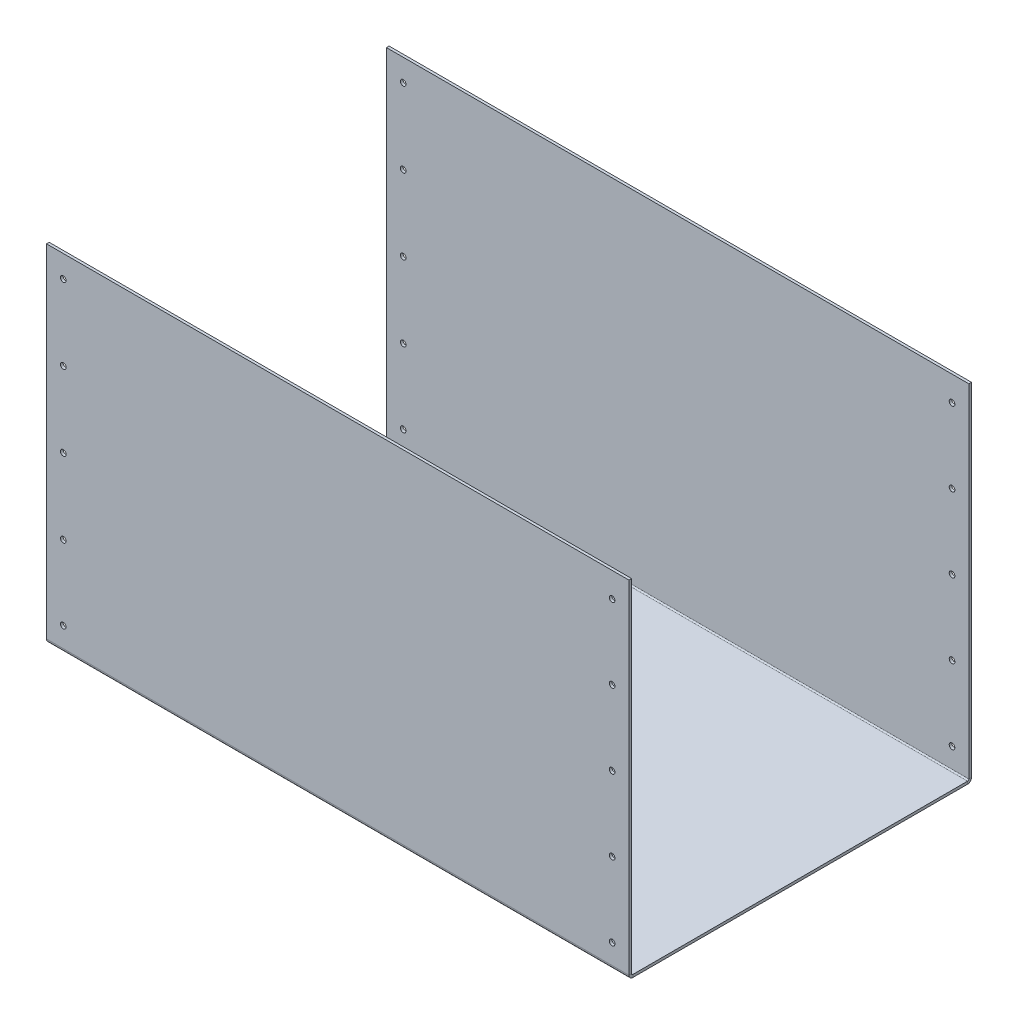
SolidWorks part; units mm, degrees
note: The reader was unsure of these and kept them because the rebuilt part matched: flange length of "Ребро-кромка1".
ref_plane "Спереди" through (0, 0, 0) normal (0, 0, 1) x (1, 0, 0)
ref_plane "Сверху" through (0, 0, 0) normal (0, 1, 0) x (1, 0, 0)
ref_plane "Справа" through (0, 0, 0) normal (1, 0, 0) x (0, 0, -1)
sketch "Эскиз1" plane through (0, 0, 0) normal (0, 1, 0) x (1, 0, 0)
  line L1 (-162.679, 129.9004) -> (166.321, 129.9004)
  line L2 (-162.679, 129.9004) -> (-162.679, -63.5996)
  line L3 (-162.679, -63.5996) -> (166.321, -63.5996)
  line L4 (166.321, 129.9004) -> (166.321, -63.5996)
  dimension "D1" = 329
  dimension "D2" = 193.5
base flange "Базовая кромка1" sketch "Эскиз1" thickness 1.5 reverse thickness direction no parameters "D1"=0.7366
edge flange "Ребро-кромка1" sketch "Эскиз18" flange profiles "Эскиз18", "Эскиз19" flange angle 90 flange length 194 flange position material inside bend radius 0.7366 thickness 1.5 relief rectangular parameters "D6"=10, "D8"=1
sketch "Эскиз18" plane through (0, 0, -129.9004) normal (0, 0, -1) x (-1, 0, 0)
  line L2 (-166.321, 0) -> (-166.321, 194)
  line L3 (-166.321, 194) -> (162.679, 194)
  line L4 (162.679, 194) -> (162.679, 0)
  line L5 (-166.321, 0) -> (162.679, 0) construction
  line L6 (-166.321, 0) -> (162.679, 0)
sketch "Эскиз19" plane through (0, 0, 63.5996) normal (0, 0, 1) x (1, 0, 0)
  line L0 (-162.679, 0) -> (166.321, 0) construction
  line L1 (-162.679, 0) -> (166.321, 0)
  line L2 (-162.679, 0) -> (-162.679, 194)
  line L3 (-162.679, 194) -> (166.321, 194)
  line L4 (166.321, 194) -> (166.321, 0)
bend "EdgeBend1" bend radius 0.7366 bend angle 90 parameters "D5"=1
bend "EdgeBend2" bend radius 0.7366 bend angle 90 parameters "D5"=2
sketch "Эскиз21" plane through (0, 0, -129.9004) normal (0, 0, -1) x (-1, 0, 0)
  line L0 (162.679, -1.5) -> (-166.321, -1.5) construction
  line L1 (-166.321, 194) -> (-166.321, 0.7366) construction
  line L2 (153.179, 181.5) -> (153.179, 12) construction
  line L3 (162.679, 0.7366) -> (162.679, 194) construction
  circle A0 centre (-156.821, 12) radius 1.6
  circle A1 centre (-156.821, 54) radius 1.6
  circle A2 centre (-156.821, 96) radius 1.6
  circle A3 centre (-156.821, 138) radius 1.6
  circle A4 centre (-156.821, 180) radius 1.6
  circle A5 centre (153.179, 181.5) radius 1.6
  circle A6 centre (153.179, 139) radius 1.6
  circle A7 centre (153.179, 96.5) radius 1.6
  circle A8 centre (153.179, 54) radius 1.6
  circle A9 centre (153.179, 12) radius 1.6
  dimension "D1" = 13.5
  dimension "D2" = 9.5
  dimension "D3" = 3.2
  dimension "D6" = 13.5
  dimension "D7" = 42
  dimension "D8" = 42.5
  dimension "D9" = 42.5
  dimension "D10" = 42.5
  dimension "D5" = 9.5
  dimension "D4" = 5
extrude "Вырез-Вытянуть2" cut sketch "Эскиз21" against normal blind 217 normal cut yes
sketch "Сгиб-Линии1" plane through (0, 0, 0) normal (0, 1, 0) x (1, 0, 0)
sketch "Граничная рамка1" plane through (0, 0, 0) normal (0, 1, 0) x (1, 0, 0)
sheet metal parameters "Листовой металл3" thickness 1.5 parameters "D1"=0.7366
flat pattern "Развертка3" [suppressed]
sketch "Сгиб-Линии2" plane through (0, 0, 0) normal (0, 1, 0) x (1, 0, 0)
sketch "Граничная рамка2" [suppressed] plane through (0, 0, 0) normal (0, 1, 0) x (1, 0, 0)
sheet metal parameters "Листовой металл4" thickness 1.5 parameters "D1"=0.7366
flat pattern "Развертка3" [suppressed]
sketch "Сгиб-Линии2" plane through (0, 0, 0) normal (0, 1, 0) x (1, 0, 0)
sketch "Граничная рамка2" [suppressed] plane through (0, 0, 0) normal (0, 1, 0) x (1, 0, 0)
bend of the flat pattern "Плоское состояние-<EdgeBend1>1"
bend of the flat pattern "Плоское состояние-<EdgeBend2>1"
sheet metal parameters "Листовой металл6" thickness 1.5 parameters "D1"=0.7366
flat pattern "Развертка3" [suppressed]
sketch "Сгиб-Линии2" plane through (0, 0, 0) normal (0, 1, 0) x (1, 0, 0)
sketch "Граничная рамка2" [suppressed] plane through (0, 0, 0) normal (0, 1, 0) x (1, 0, 0)
bend of the flat pattern "Плоское состояние-<EdgeBend1>1"
bend of the flat pattern "Плоское состояние-<EdgeBend2>1"
